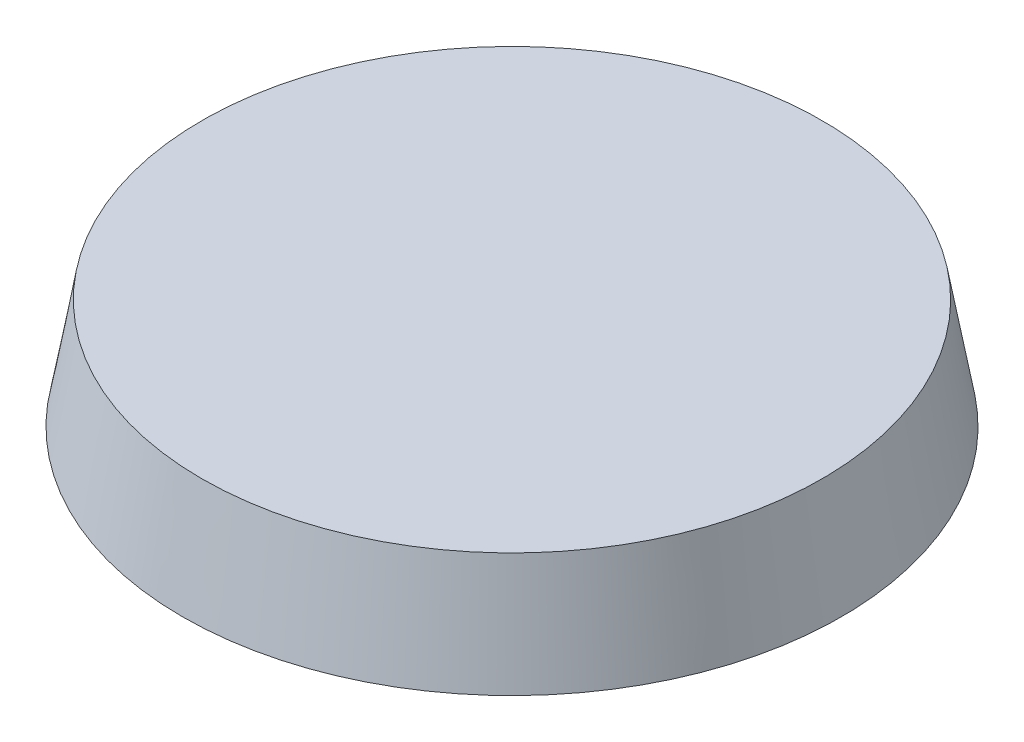
SolidWorks part; units mm, degrees
material "AISI 1020"
ref_plane "Front Plane" through (0, 0, 0) normal (0, 0, 1) x (1, 0, 0)
ref_plane "Top Plane" through (0, 0, 0) normal (0, 1, 0) x (1, 0, 0)
ref_plane "Right Plane" through (0, 0, 0) normal (1, 0, 0) x (0, 0, -1)
sketch "Sketch2" plane through (0, 0, 0) normal (0, 1, 0) x (1, 0, 0)
  circle A0 centre (0, 0) radius 150
  dimension "D1" = 300
extrude "Boss-Extrude1" add sketch "Sketch2" along normal blind 50 draft 10
ref_axis "Base-Axis" through (0, 0, 0) along (0, 1, 0)
